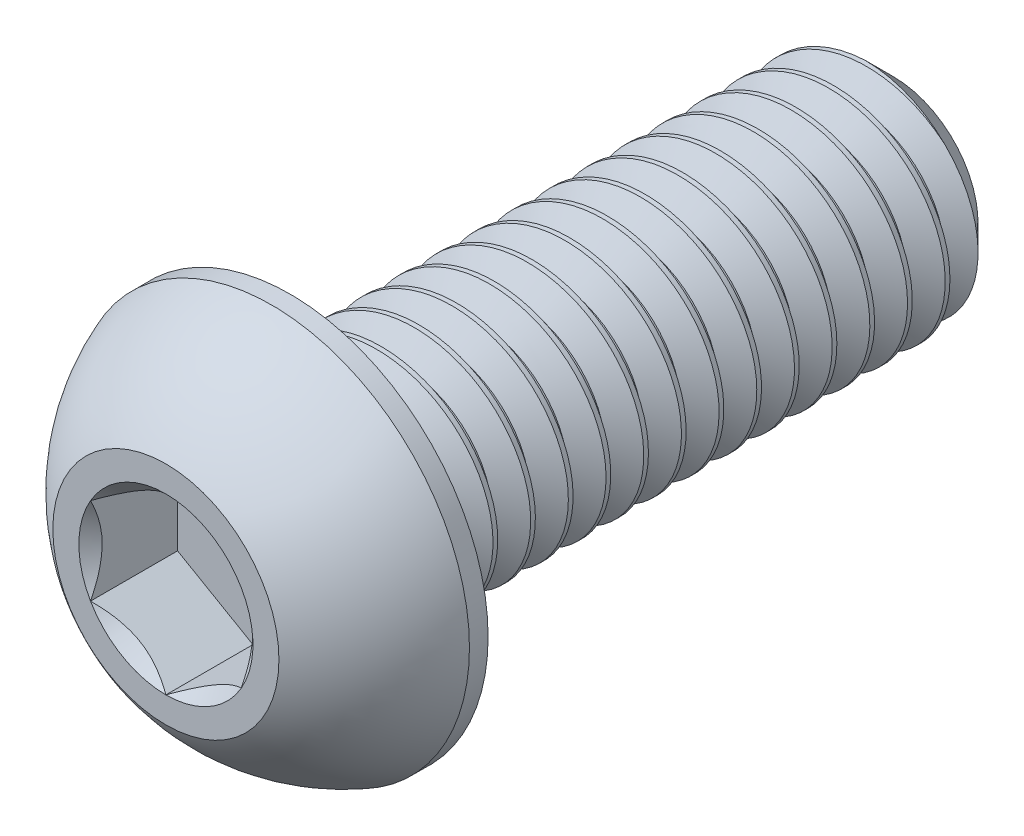
SolidWorks part; units mm, degrees
note: '?' marks a value the reader was unsure of.
ref_plane "Front" through (0, 0, 0) normal (0, 0, 1) x (1, 0, 0)
ref_plane "Top" through (0, 0, 0) normal (0, 1, 0) x (1, 0, 0)
ref_plane "Right" through (0, 0, 0) normal (1, 0, 0) x (0, 0, -1)
sketch "Sketch1" plane through (0, 0, 0) normal (1, 0, 0) x (0, 0, -1)
  line L2 (3.3, 3) -> (19.3, 3)
  line L3 (19.3, 3) -> (19.3, 0)
  line L4 (19.3, 0) -> (3.3, 0)
  line L6 (2.805, 5.25) -> (3.3, 5.25) construction
  line L7 (19.3, 3) -> (19.3, -3) construction
  line L8 (0, 0) -> (3.3, 0) construction
  line L9 (3.3, 5.25) -> (3.3, -5.25) construction
  line L11 (3.3, 3) -> (3.3, 0)
  line L13 (0, 2) -> (0, -2) construction
  line L14 (0, 2) -> (0, 3) construction
  arc A3 (0, 3) -> (2.805, 5.25) centre (4.7113, 0) cw construction
  dimension "D1" = 0.495
  dimension "Head Ht" = 3.3
  dimension "Head Dia" = 10.5
  dimension "Dia" = 6
  dimension "Lg" = 16
  dimension "Hex" = 4
revolve "Revolve1" add sketch "Sketch1" angle 360 mid plane about L4
sketch "Sketch3" plane through (0, 0, -19.3) normal (0, 0, -1) x (-1, 0, 0)
  circle A0 centre (0, 0) radius 3
curve "Helix/Spiral1" pitch 1 height 17 turns 17
chamfer "Chamfer1" distance 0.75 angle 45 1 edges at (0, 3, -19.3)
sketch "Sketch7" plane through (0, 0, 0) normal (1, 0, 0) x (0, 0, -1)
  line L6 (2.805, 5.25) -> (3.3, 5.25) construction
  line L8 (0, 0) -> (3.3, 0) construction
  line L11 (3.3, 5.25) -> (3.3, -5.25) construction
  line L12 (2.805, 5.25) -> (3.3, 5.25)
  line L13 (0, 0) -> (3.3, 0)
  line L14 (0, 2) -> (0, -2) construction
  line L15 (3.3, 5.25) -> (3.3, 0)
  line L16 (0, 3) -> (0, 0)
  arc A2 (2.805, 5.25) -> (0, 3) centre (4.7113, 0) ccw construction
  arc A3 (2.805, 5.25) -> (0, 3) centre (4.7113, 0) ccw
revolve "Revolve2" add sketch "Sketch7" angle 360 mid plane about L13
sketch "Sketch5" plane through (0, 0, 0) normal (0, 0, 1) x (1, 0, 0)
  line L1 (2, -1.1547) -> (2, 1.1547)
  line L2 (2, 1.1547) -> (0, 2.3094)
  line L3 (0, 2.3094) -> (-2, 1.1547)
  line L4 (-2, 1.1547) -> (-2, -1.1547)
  line L5 (-2, -1.1547) -> (0, -2.3094)
  line L6 (0, -2.3094) -> (2, -1.1547)
  circle A0 centre (0, 0) radius 2 construction
extrude "Cut-Extrude2" cut sketch "Sketch5" against normal blind 2.31
sketch "Sketch6" plane through (0, 0, 0) normal (0, 0, 1) x (1, 0, 0)
  circle A0 centre (0, 0) radius 2.3094
extrude "Cut-Extrude3" cut sketch "Sketch6" against normal blind 2.31 draft 45
sketch "Sketch2" plane through (0, 0, 0) normal (1, 0, 0) x (0, 0, -1)
  line L0 (18.55, 3) -> (19.425, 3)
  line L1 (19.425, 3) -> (19.05, 2.3505)
  line L2 (19.05, 2.3505) -> (18.925, 2.3505)
  line L3 (18.925, 2.3505) -> (18.55, 3)
  line L4 (18.7375, 2.6752) -> (19.2375, 2.6752) construction
  dimension "D1" = 60
  dimension "D2" = 0.125
  dimension "D3" = 0.5
sweep "Cut-Sweep1" cut profiles "Sketch2" path "Helix/Spiral1"
sketch "Sketch10" plane through (0, 0, 0) normal (1, 0, 0) x (0, 0, -1)
  line L0 (19.3, 3) -> (19.3, -3) construction
  point P0 (17.8, -3)
  dimension "D1" = 1.5
ref_axis "Center Axis 1" through (0, 0, -8.1113) along (0, 0, 1)?
ref_plane "Contact Plane 1" through (0, 0, -3.3) normal (0, 0, -1) x (-1, 0, 0)
ref_plane "Contact Plane 2" through (0, 0, 0) normal (0, 0, 1) x (1, 0, 0)
equation "\"D3@Helix/Spiral1\" = \"Lg@Sketch1\" + \"D4@Helix/Spiral1\""
equation "\"D2@Sketch2\" = \"D4@Helix/Spiral1\" * .125"
equation "\"D3@Sketch2\" = \"D4@Helix/Spiral1\" * .5"
equation "\"D1@Chamfer1\" = \"D4@Helix/Spiral1\" * .75"
equation "\"D1@Cut-Extrude2\" = \"Head Ht@Sketch1\" * .7"
equation "\"D1@Sketch1\" = \"Head Ht@Sketch1\" * .15"
equation "\"D1@Sketch10\" = \"D4@Helix/Spiral1\" * 1.5"
equation "\"D1@Cut-Extrude3\" = \"D1@Cut-Extrude2\""
